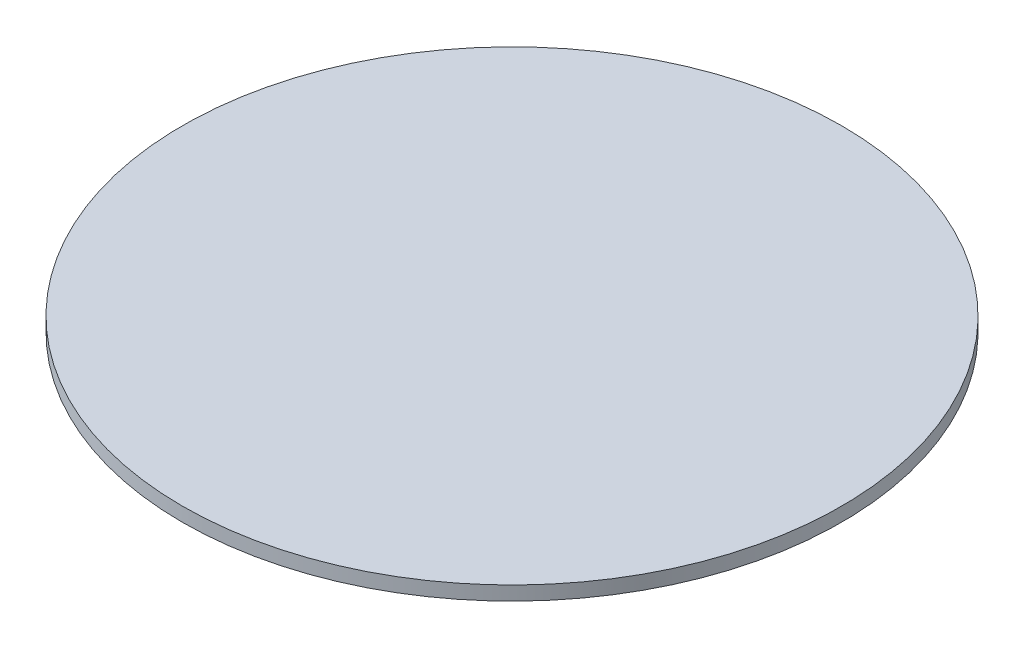
SolidWorks part; units mm, degrees
material "AISI 304"
ref_plane "前视基准面" through (0, 0, 0) normal (0, 0, 1) x (1, 0, 0)
ref_plane "上视基准面" through (0, 0, 0) normal (0, 1, 0) x (1, 0, 0)
ref_plane "右视基准面" through (0, 0, 0) normal (1, 0, 0) x (0, 0, -1)
sketch "Sketch1" plane through (0, 0, 0) normal (0, 1, 0) x (1, 0, 0)
  circle A0 centre (0, 0) radius 47.0878
base flange "Base-Flange1" sketch "Sketch1" thickness 2 reverse thickness direction no parameters "D1"=0.7366
sketch "Bend-Lines1" plane through (0, 0, 0) normal (0, 1, 0) x (1, 0, 0)
sketch "Bounding-Box1" plane through (0, 0, 0) normal (0, 1, 0) x (1, 0, 0)
sheet metal parameters "Sheet-Metal6" thickness 2 parameters "D1"=0.7366
flat pattern "Flat-Pattern6" [suppressed]
sketch "Bend-Lines2" plane through (0, 0, 0) normal (0, 1, 0) x (1, 0, 0)
sketch "Bounding-Box2" [suppressed] plane through (0, 0, 0) normal (0, 1, 0) x (1, 0, 0)
